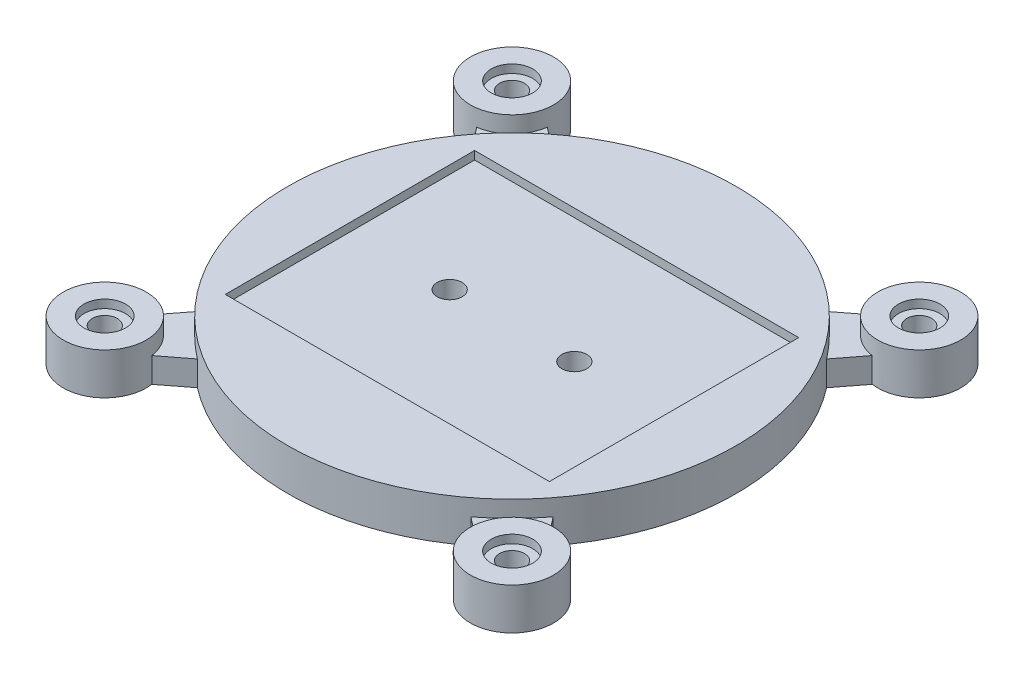
SolidWorks part; units mm, degrees
ref_plane "Front Plane" through (0, 0, 0) normal (0, 0, 1) x (1, 0, 0)
ref_plane "Top Plane" through (0, 0, 0) normal (0, 1, 0) x (1, 0, 0)
ref_plane "Right Plane" through (0, 0, 0) normal (1, 0, 0) x (0, 0, -1)
sketch "Sketch1" plane through (0, 0, 0) normal (0, 1, 0) x (1, 0, 0)
  circle A0 centre (0, 0) radius 27
  dimension "D1" = 54
extrude "Boss-Extrude1" add sketch "Sketch1" along normal blind 5
sketch "Sketch2" plane through (0, 0, 0) normal (0, 1, 0) x (1, 0, 0)
  line L0 (-19.0158, 0) -> (0, 0) construction
  line L1 (0, 0) -> (-35.8235, 35.8235) construction
  line L2 (-23.7929, 19.5503) -> (-21.4057, 16.4559)
  line L3 (-19.5503, 23.7929) -> (-16.4559, 21.4057)
  line L4 (0, 0) -> (0, 15.5957) construction
  circle A0 centre (-24.5, 24.5) radius 5
  arc A1 (-16.4559, 21.4057) -> (-21.4057, 16.4559) centre (0, 0) ccw
  circle A2 centre (0, 0) radius 27 construction
  dimension "D1" = 10
  dimension "D5" = 59
  dimension "D2" = 6
  dimension "D3" = 45
  dimension "D4" = 7
extrude "Boss-Extrude3" add sketch "Sketch2" along normal blind 3 contours A1 L3 A0 L2 region at (-20.1051, 0, -20.1051)
extrude "Boss-Extrude4" add sketch "Sketch2<3>" along normal through all contours A0 region at (-24.5, 0, -24.5)
sketch "Sketch2<3>" plane through (0, 0, 0) normal (0, 1, 0) x (1, 0, 0) same geometry as "Sketch2"
hole_wizard "CBORE for M5 Hex Head Bolt1" positions "Sketch3" profile "Sketch4" counterbore size "M5" standard "ANSI Metric" end condition through all
sketch "Sketch3" plane through (0, 5, 0) normal (0, 1, 0) x (1, 0, 0)
  point P0 (-24.5, 24.5)
sketch "Sketch4" plane through (-24.5, 5, -24.5) normal (1, 0, 0) x (0, 0, 1)
  line L0 (0, 0) -> (0, 5)
  line L1 (0, 5) -> (1.5, 5)
  line L3 (1.5, 5) -> (1.5, 1)
  line L4 (1.5, 1) -> (2.5, 1)
  line L5 (2.5, 1) -> (2.5, 0)
  line L7 (2.5, 0) -> (0, 0)
  line L11 (0, -6.35) -> (0, 107.95) construction
  dimension "Thru Hole Dia." = 3
  dimension "Thru Hole Depth" = 5
  dimension "C'Bore Dia." = 5
  dimension "C'Bore Depth" = 1
sketch "Sketch5" plane through (0, 5, 0) normal (0, 1, 0) x (1, 0, 0)
  line L1 (-19.5, -15) -> (19.5, -15)
  line L2 (-19.5, -15) -> (-19.5, 15)
  line L3 (-19.5, 15) -> (19.5, 15)
  line L4 (19.5, -15) -> (19.5, 15)
  line L5 (-19.5, -15) -> (19.5, 15) construction
  line L6 (-19.5, 15) -> (19.5, -15) construction
  point P0 (0, 0)
  dimension "D1" = 30
  dimension "D2" = 39
extrude "Cut-Extrude1" cut sketch "Sketch5" against normal blind 1
sketch "Sketch6" plane through (0, 4, 0) normal (0, 1, 0) x (1, 0, 0)
  line L0 (0, 0) -> (0, 12.5168) construction
  circle A0 centre (-7.5, 0) radius 1.5
  circle A1 centre (7.5, 0) radius 1.5
  dimension "D1" = 15
  dimension "D2" = 3
extrude "Cut-Extrude2" cut sketch "Sketch6" against normal through all
pattern_circular "CirPattern1" count 4 over 360 about axis through (0, 5, 0) along (0, 1, 0) of "Boss-Extrude3", "Boss-Extrude4", "CBORE for M5 Hex Head Bolt1"
